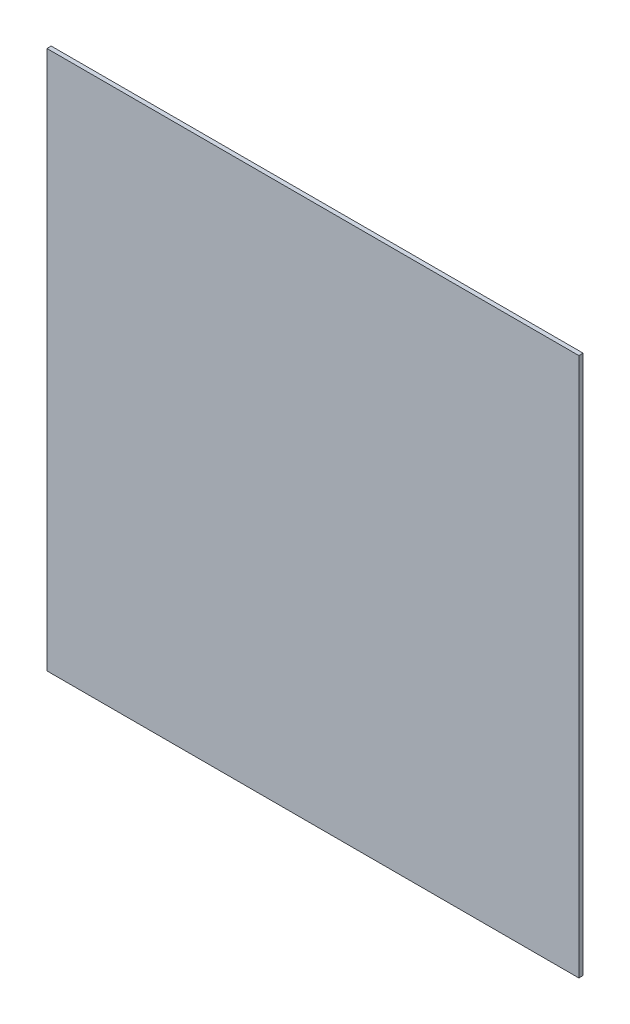
SolidWorks part; units mm, degrees
material "Glass"
ref_plane "Front Plane" through (0, 0, 0) normal (0, 0, 1) x (1, 0, 0)
ref_plane "Top Plane" through (0, 0, 0) normal (0, 1, 0) x (1, 0, 0)
ref_plane "Right Plane" through (0, 0, 0) normal (1, 0, 0) x (0, 0, -1)
sketch "Sketch1" plane through (0, 0, 0) normal (0, 0, 1) x (1, 0, 0)
  line L1 (-187.5, -190) -> (187.5, -190)
  line L2 (-187.5, -190) -> (-187.5, 190)
  line L3 (-187.5, 190) -> (187.5, 190)
  line L4 (187.5, -190) -> (187.5, 190)
  line L5 (-187.5, -190) -> (187.5, 190) construction
  line L6 (-187.5, 190) -> (187.5, -190) construction
  point P0 (0, 0)
  dimension "D1" = 375
  dimension "D2" = 380
extrude "Boss-Extrude1" add sketch "Sketch1" along normal mid plane 3
sketch "Sketch2" [suppressed] plane through (0, 0, 1.5) normal (0, 0, 1) x (1, 0, 0)
  line L0 (106, 140) -> (104, 140) construction
  line L1 (-155.214, 211.8255) -> (203.9552, 211.8255)
  line L2 (-155.214, 211.8255) -> (-155.214, 140)
  line L3 (-155.214, 140) -> (203.9552, 140)
  line L4 (203.9552, 211.8255) -> (203.9552, 140)
extrude "Cut-Extrude1" [suppressed] cut sketch "Sketch2" against normal through all
